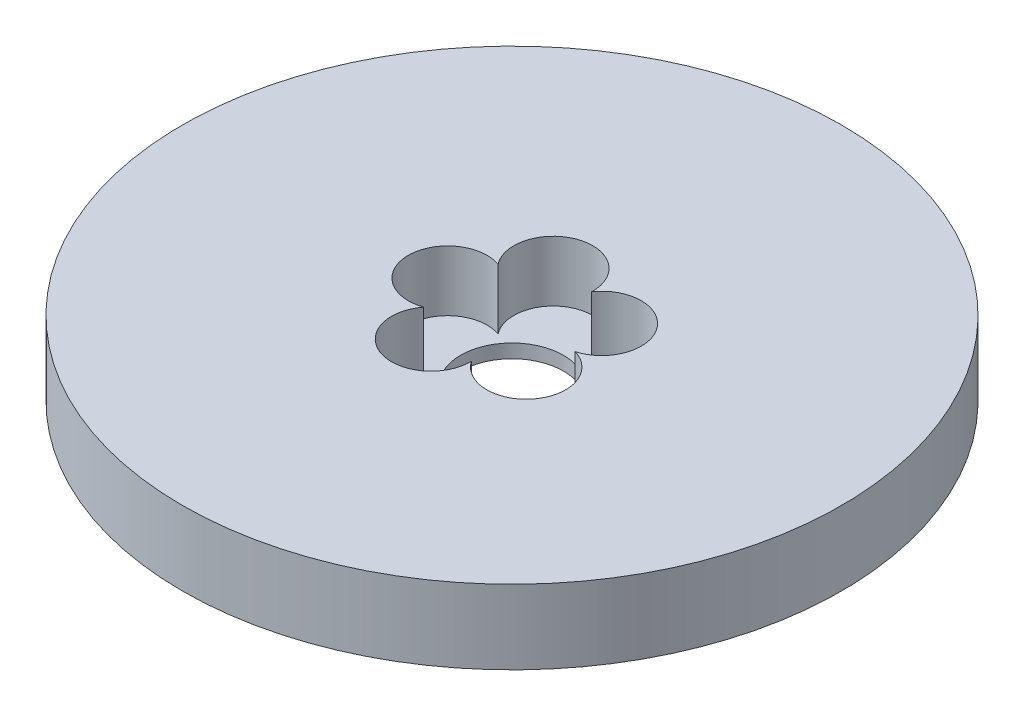
SolidWorks part; units mm, degrees
ref_plane "Front Plane" through (0, 0, 0) normal (0, 0, 1) x (1, 0, 0)
ref_plane "Top Plane" through (0, 0, 0) normal (0, 1, 0) x (1, 0, 0)
ref_plane "Right Plane" through (0, 0, 0) normal (1, 0, 0) x (0, 0, -1)
sketch "Sketch1" plane through (0, 0, 0) normal (0, 1, 0) x (1, 0, 0)
  circle A0 centre (0, 0) radius 80
  dimension "FLANGE_OD" = 160
extrude "Boss-Extrude1" add sketch "Sketch1" along normal blind 18
sketch "Sketch2" plane through (0, 0, 0) normal (0, 1, 0) x (1, 0, 0)
  circle A0 centre (0, 0) radius 12.5
  dimension "BORE_D" = 25
extrude "Cut-Extrude1" cut sketch "Sketch2" along normal through all
sketch "Sketch3" plane through (0, 18, 0) normal (0, 1, 0) x (1, 0, 0)
  circle A0 centre (0, 0) radius 15.6128 construction
  circle A1 centre (-15.6128, 0) radius 9.5716
  dimension "BOLT_D" = 19.1432
  dimension "BOLT_PCD" = 31.2256
extrude "Cut-Extrude2" cut sketch "Sketch3" against normal blind 14.6739
pattern_circular "CirPattern1" count 5 over 360 about axis through (0, 0, 0) along (0, 1, 0) of "Cut-Extrude2"
